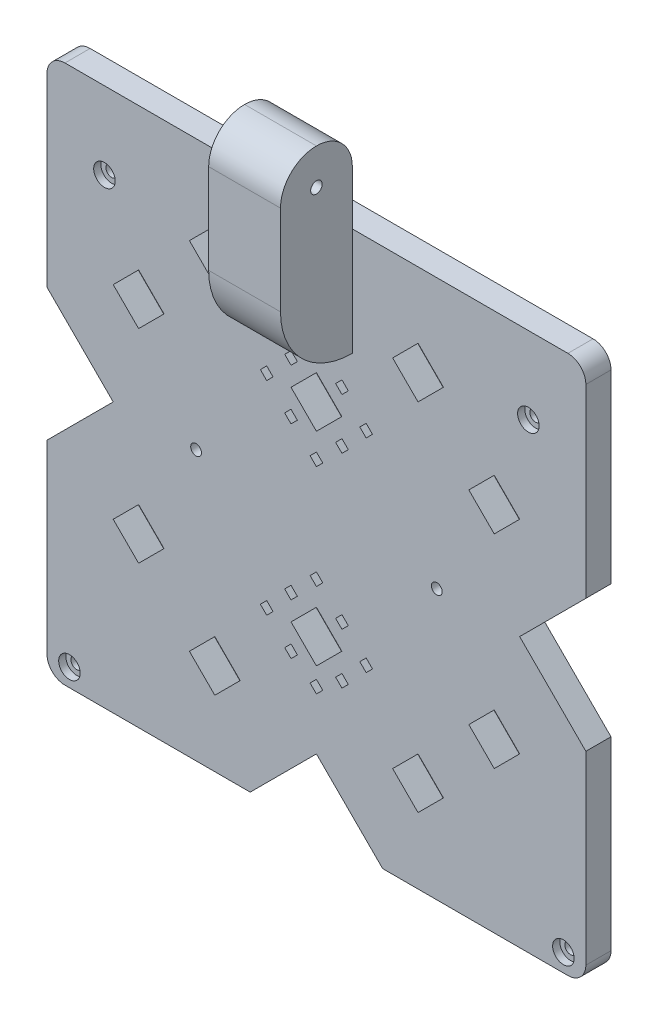
SolidWorks part; units mm, degrees
ref_plane "前基準面" through (0, 0, 0) normal (0, 0, 1) x (1, 0, 0)
ref_plane "上基準面" through (0, 0, 0) normal (0, 1, 0) x (1, 0, 0)
ref_plane "右基準面" through (0, 0, 0) normal (1, 0, 0) x (0, 0, -1)
sketch "草圖1" plane through (0, 0, 0) normal (0, 0, 1) x (1, 0, 0)
  line L1 (-75, 75) -> (75, 75)
  line L2 (-75, 75) -> (-75, -75)
  line L3 (-75, -75) -> (75, -75)
  line L4 (75, 75) -> (75, -75)
  line L5 (-75, 75) -> (75, -75) construction
  line L6 (-75, -75) -> (75, 75) construction
  point P0 (0, 0)
  dimension "D1" = 150
  dimension "D2" = 150
extrude "填料-伸長1" add sketch "草圖1" along normal blind 7 contours L2 L1 L4 L3
sketch "草圖2" plane through (0, 0, 7) normal (0, 0, 1) x (1, 0, 0)
  line L0 (-75, 75) -> (75, -75)
  line L1 (-75, -75) -> (75, 75)
  line L7 (-33.5, 33.5) -> (33.5, -33.5) construction
  line L8 (-33.5, -33.5) -> (33.5, 33.5) construction
  line L21 (-75, 18.8557) -> (18.8557, -75)
  line L22 (-75, 18.4315) -> (18.4315, -75)
  line L23 (-75, 75) -> (-75, -75) construction
  line L24 (-75, -75) -> (75, -75) construction
  line L25 (-18.4315, 75) -> (75, -18.4315)
  line L26 (-75, 75) -> (75, 75) construction
  line L27 (75, 75) -> (75, -75) construction
  line L28 (18.4315, 75) -> (-75, -18.4315)
  line L29 (75, 18.4315) -> (-18.4315, -75)
  line L35 (-75, -18.4315) -> (-56.5685, 0)
  line L36 (-56.5685, 0) -> (-75, 18.4315)
  line L37 (-18.4315, 75) -> (0, 56.5685)
  line L38 (0, 56.5685) -> (18.4315, 75)
  line L39 (-18.4315, 75) -> (18.4315, 75)
  line L40 (75, 18.4315) -> (75, -18.4315)
  line L41 (56.5685, 0) -> (75, 18.4315)
  line L42 (-18.4315, -75) -> (18.4315, -75)
  line L43 (0, -56.5685) -> (-18.4315, -75)
  line L44 (0, -56.5685) -> (18.4315, -75)
  line L45 (-75, 18.8557) -> (-75, 18.4315)
  line L46 (18.8557, -75) -> (18.4315, -75)
  line L47 (-18.8557, -75) -> (-18.4315, -75)
  line L48 (-18.8557, -75) -> (75, 18.8557)
  line L49 (75, 18.8557) -> (75, 18.4315)
  line L50 (-18.8557, 75) -> (-18.4315, 75)
  line L51 (-18.8557, 75) -> (75, -18.8557)
  line L52 (75, -18.8557) -> (75, -18.4315)
  line L53 (18.4315, 75) -> (18.8557, 75)
  line L54 (18.8557, 75) -> (-75, -18.8557)
  line L55 (-75, -18.8557) -> (-75, -18.4315)
  point P8 (0, 0)
  dimension "D8" = 40
  dimension "D2" = 0.3
  dimension "D3" = 0.3
  dimension "D4" = 0.3
  dimension "D5" = 0.3
  dimension "D9" = 40
  dimension "D10" = 40
  dimension "D11" = 40
sketch "草圖3" plane through (0, 0, 7) normal (0, 0, 1) x (1, 0, 0)
  line L0 (-75, 18.4315) -> (-56.5685, 0)
  line L1 (-56.5685, 0) -> (-75, -18.4315)
  line L2 (-75, -18.4315) -> (-75, 18.4315)
  line L3 (18.4315, -75) -> (-18.4315, -75)
  line L4 (-18.4315, -75) -> (0, -56.5685)
  line L5 (0, -56.5685) -> (18.4315, -75)
  line L6 (75, 18.4315) -> (75, -18.4315)
  line L7 (75, -18.4315) -> (56.5685, 0)
  line L8 (56.5685, 0) -> (75, 18.4315)
  line L9 (-18.4315, 75) -> (18.4315, 75)
  line L10 (18.4315, 75) -> (0, 56.5685)
  line L11 (0, 56.5685) -> (-18.4315, 75)
extrude "除料-伸長1" cut sketch "草圖3" against normal blind 7 contours L8 L6 L7 | L5 L3 L4 | L2 L0 L1
sketch "草圖7" plane through (0, 75, 0) normal (0, 1, 0) x (1, 0, 0)
  line L6 (0, 0) -> (0, -7)
  line L7 (-75, 0) -> (75, 0) construction
  line L8 (-75, -7) -> (75, -7) construction
  line L10 (-7.5, 0) -> (7.5, 0)
  line L11 (-7.5, 0) -> (-7.5, -7)
  line L12 (-7.5, -7) -> (7.5, -7)
  line L13 (7.5, 0) -> (7.5, -7)
  line L14 (-7.5, 0) -> (7.5, -7) construction
  line L15 (-7.5, -7) -> (7.5, 0) construction
  point P6 (0, -3.5)
  dimension "D1" = 15
sketch "草圖11" plane through (0, 0, 7) normal (0, 0, 1) x (1, 0, 0)
  line L5 (-28.5, 33.5) -> (-28.5, -33.5)
  line L6 (-28.5, -33.5) -> (28.5, -33.5)
  line L7 (-28.5, -33.5) -> (-28.5, 33.5)
  line L8 (-28.5, 33.5) -> (28.5, 33.5)
  line L9 (28.5, -33.5) -> (28.5, 33.5)
  line L10 (-28.5, -33.5) -> (28.5, 33.5) construction
  line L11 (-28.5, 33.5) -> (28.5, -33.5) construction
  line L13 (-38.5, 0) -> (-38.5, 5)
  line L14 (-38.5, 5) -> (-28.5, 5)
  line L15 (-28.5, 5) -> (-28.5, 0)
  line L16 (-28.5, 0) -> (-28.5, -5)
  line L17 (-28.5, -5) -> (-38.5, -5)
  line L18 (-38.5, -5) -> (-38.5, 0)
  line L19 (-38.5, 5) -> (-28.5, -5)
  line L20 (-28.5, 5) -> (28.5, 5)
  line L21 (28.5, 5) -> (38.5, 5)
  line L22 (38.5, 5) -> (38.5, -5)
  line L23 (38.5, -5) -> (28.5, -5)
  line L24 (28.5, 5) -> (38.5, -5)
  circle A0 centre (-33.5, 0) radius 1.5
  circle A1 centre (33.5, 0) radius 1.5
  point P0 (0, 0)
  point P20 (0, 0)
  dimension "D4" = 10
  dimension "D1" = 67
  dimension "D2" = 67
  dimension "D3" = 10
extrude "除料-伸長3" cut sketch "草圖11" against normal blind 7 contours A0 | A1
sketch "草圖12" plane through (0, 0, 0) normal (0, 0, -1) x (-1, 0, 0)
  line L0 (-75, -65) -> (75, -65)
  line L1 (-75, -18.4315) -> (-75, -75) construction
  line L2 (75, -18.4315) -> (75, -75) construction
  line L3 (-62.5, -75) -> (-62.5, 75)
  line L4 (-18.4315, -75) -> (-75, -75) construction
  line L5 (75, 75) -> (-75, 75) construction
  line L6 (62.5, 75) -> (62.5, -75)
  line L7 (75, 75) -> (-75, 75) construction
  line L8 (75, -75) -> (18.4315, -75) construction
  line L9 (-75, -65) -> (-62.5, -75)
  line L10 (62.5, -65) -> (75, -75)
  line L11 (-65.17, -70) -> (-66.96, -66.8996)
  line L12 (-66.96, -66.8996) -> (-70.54, -66.8996)
  line L13 (-70.54, -66.8996) -> (-72.33, -70)
  line L14 (-72.33, -70) -> (-70.54, -73.1004)
  line L15 (-70.54, -73.1004) -> (-66.96, -73.1004)
  line L16 (-66.96, -73.1004) -> (-65.17, -70)
  line L18 (72.33, -70) -> (70.54, -66.8996)
  line L19 (70.54, -66.8996) -> (66.96, -66.8996)
  line L20 (66.96, -66.8996) -> (65.17, -70)
  line L21 (65.17, -70) -> (66.96, -73.1004)
  line L22 (66.96, -73.1004) -> (70.54, -73.1004)
  line L23 (70.54, -73.1004) -> (72.33, -70)
  circle A0 centre (-68.75, -70) radius 3.1004 construction
  circle A1 centre (68.75, -70) radius 3.1004 construction
  dimension "D1" = 12.5
  dimension "D2" = 12.5
  dimension "D3" = 10
  dimension "D4" = 3.58
  dimension "D5" = 3.58
extrude "除料-伸長4" cut sketch "草圖12" against normal blind 0.5 contours L12 L13 L14 L15 L16 L11 | L18 L19 L20 L21 L22 L23
sketch "草圖13" plane through (0, 0, 0.5) normal (0, 0, -1) x (-1, 0, 0)
  line L0 (-70.54, -66.8996) -> (-66.96, -73.1004)
  line L1 (66.96, -66.8996) -> (70.54, -73.1004)
  line L2 (-65.52, -70) -> (-67.135, -67.2027)
  line L3 (-67.135, -67.2027) -> (-70.365, -67.2027)
  line L4 (-70.365, -67.2027) -> (-71.98, -70)
  line L5 (-71.98, -70) -> (-70.365, -72.7973)
  line L6 (-70.365, -72.7973) -> (-67.135, -72.7973)
  line L7 (-67.135, -72.7973) -> (-65.52, -70)
  line L9 (71.98, -70) -> (70.365, -67.2027)
  line L10 (70.365, -67.2027) -> (67.135, -67.2027)
  line L11 (67.135, -67.2027) -> (65.52, -70)
  line L12 (65.52, -70) -> (67.135, -72.7973)
  line L13 (67.135, -72.7973) -> (70.365, -72.7973)
  line L14 (70.365, -72.7973) -> (71.98, -70)
  circle A0 centre (-68.75, -70) radius 2.7973 construction
  circle A1 centre (68.75, -70) radius 2.7973 construction
  dimension "D1" = 3.23
  dimension "D2" = 3.23
extrude "除料-伸長5" cut sketch "草圖13" against normal blind 2 contours L11 L12 L13 L14 L9 L10 | L3 L4 L5 L6 L7 L2
sketch "草圖14" plane through (0, 0, 2.5) normal (0, 0, -1) x (-1, 0, 0)
  line L0 (65.52, -70) -> (71.98, -70)
  line L1 (-71.98, -70) -> (-65.52, -70)
  circle A0 centre (68.75, -70) radius 1.6
  circle A1 centre (-68.75, -70) radius 1.6
extrude "除料-伸長6" cut sketch "草圖14" against normal blind 3.5 contours A1 | A0
sketch "草圖15" plane through (0, 0, 0) normal (0, 0, -1) x (-1, 0, 0)
  line L0 (-62.5032, 75) -> (-62.5032, -75)
  line L1 (75, 75) -> (-75, 75) construction
  line L2 (-18.4315, -75) -> (-75, -75) construction
  line L3 (62.5, 75) -> (62.5, -75)
  line L4 (75, 75) -> (-75, 75) construction
  line L5 (75, -75) -> (18.4315, -75) construction
  line L6 (-75, -18.4315) -> (-75, -75) construction
  line L7 (75, -18.4315) -> (75, -75) construction
  line L8 (-62.5032, 50) -> (62.5, 50)
  line L10 (75, 75) -> (75, 18.4315) construction
  line L11 (75, 46.7157) -> (75, 75)
  line L12 (-62.5032, 57) -> (62.5, 57)
  line L15 (-55.5032, 57) -> (-55.5032, 50)
  line L16 (55.5, 57) -> (55.5, 50)
  line L17 (55.5, 57) -> (62.5, 50)
  line L18 (-62.5032, 57) -> (-55.5032, 50)
  circle A0 centre (59, 53.5) radius 1.6
  circle A1 centre (-59.0032, 53.5) radius 1.6
  dimension "D1" = 12.4968
  dimension "D2" = 12.5
  dimension "D3" = 125
  dimension "D4" = 7
  dimension "D5" = 7
  dimension "D6" = 7
extrude "除料-伸長7" cut sketch "草圖15" against normal blind 7 contours A1 | A0
sketch "草圖16" plane through (0, 0, 0) normal (0, 0, -1) x (-1, 0, 0)
  line L0 (75, 75) -> (-75, 75) construction
  line L5 (-17.5, 45) -> (17.5, 45)
  line L6 (-17.5, 45) -> (-17.5, 75)
  line L7 (-17.5, 75) -> (17.5, 75)
  line L8 (17.5, 45) -> (17.5, 75)
  line L9 (-17.5, 45) -> (17.5, 75) construction
  line L10 (-17.5, 75) -> (17.5, 45) construction
  line L11 (18.4315, 75) -> (-18.4315, 75) construction
  line L12 (0, 75) -> (0, 60)
  point P0 (-0.3693, 67.6901)
  dimension "D1" = 35
  dimension "D2" = 30
sketch "草圖18" plane through (0, 0, 7) normal (0, 0, 1) x (1, 0, 0)
  line L0 (0, 75) -> (0, 60)
  line L10 (0, 75) -> (-10, 75)
  line L11 (0, 75) -> (10, 75)
  line L12 (-10, 75) -> (-10, 45)
  line L13 (10, 75) -> (10, 45)
  line L14 (10, 45) -> (-10, 45)
  dimension "D1" = 10
  dimension "D2" = 10
extrude "填料-伸長6" add sketch "草圖18" along normal blind 20
fillet "圓角5" radius 20 1 edges at (0, 45, 27)
sketch "草圖20" plane through (0, 75, 0) normal (0, 1, 0) x (1, 0, 0)
  line L1 (-10, -7) -> (10, -7)
  line L2 (-10, -7) -> (-10, -27)
  line L3 (-10, -27) -> (10, -27)
  line L4 (10, -7) -> (10, -27)
extrude "填料-伸長7" add sketch "草圖20" along normal blind 25
fillet "圓角6" radius 10 2 edges at (0, 100, 7) (0, 100, 27)
sketch "草圖21" plane through (-10, 0, 0) normal (-1, 0, 0) x (0, 0, 1)
  circle A0 centre (17, 90) radius 1.6
extrude "除料-伸長8" cut sketch "草圖21" against normal blind 35
sketch "草圖24" plane through (0, 0, 7) normal (0, 0, -1) x (-1, 0, 0)
  line L0 (-10.3123, 85.7865) -> (-30.4726, 85.7865)
  line L1 (-10, 90) -> (-10, 75) construction
  line L2 (-30.4726, 85.7865) -> (-30.4726, 83.7865)
  line L3 (-30.4726, 83.7865) -> (-10, 83.7865)
  line L4 (-10, 83.7865) -> (9.6877, 83.7865)
  line L6 (9.6877, 83.7865) -> (29.5274, 83.7865)
  line L7 (29.5274, 83.7865) -> (29.5274, 85.7865)
  line L8 (29.5274, 85.7865) -> (9.6877, 85.7865)
  line L9 (9.6877, 85.7865) -> (-10.3123, 85.7865)
  dimension "D1" = 2
  dimension "D2" = 60
sketch "草圖25" plane through (0, 0, 7) normal (0, 0, 1) x (1, 0, 0)
  line L0 (0, -75) -> (0, 75) construction
  line L2 (75, 0) -> (-75, 0) construction
  line L5 (-28.2843, -28.2843) -> (-75, -28.2843) construction
  line L6 (-42.4264, -28.2843) -> (-49.4975, -21.2132)
  line L7 (-49.4975, -21.2132) -> (-56.5685, -28.2843)
  line L8 (-56.5685, -28.2843) -> (-49.4975, -35.3553)
  line L9 (-49.4975, -35.3553) -> (-42.4264, -28.2843)
  line L10 (-75, 18.4315) -> (18.4315, -75) construction
  line L11 (-75, -18.4315) -> (-75, -75) construction
  line L12 (-28.2843, -28.2843) -> (-28.2843, -75) construction
  line L13 (-75, -75) -> (-18.4315, -75) construction
  line L14 (-75, -75) -> (75, 75) construction
  line L15 (-21.2132, -49.4975) -> (-28.2843, -42.4264)
  line L16 (-28.2843, -42.4264) -> (-35.3553, -49.4975)
  line L17 (-35.3553, -49.4975) -> (-28.2843, -56.5685)
  line L18 (-28.2843, -56.5685) -> (-21.2132, -49.4975)
  line L19 (75, 18.4315) -> (75, -18.4315) construction
  line L20 (-18.4315, -75) -> (18.4315, -75) construction
  line L21 (-28.2843, 56.5685) -> (-21.2132, 49.4975)
  line L22 (-35.3553, 49.4975) -> (-28.2843, 56.5685)
  line L23 (-28.2843, 42.4264) -> (-35.3553, 49.4975)
  line L24 (-21.2132, 49.4975) -> (-28.2843, 42.4264)
  line L25 (-49.4975, 35.3553) -> (-42.4264, 28.2843)
  line L26 (-56.5685, 28.2843) -> (-49.4975, 35.3553)
  line L27 (-49.4975, 21.2132) -> (-56.5685, 28.2843)
  line L28 (-42.4264, 28.2843) -> (-49.4975, 21.2132)
  line L29 (28.2843, -56.5685) -> (21.2132, -49.4975)
  line L30 (35.3553, -49.4975) -> (28.2843, -56.5685)
  line L31 (28.2843, -42.4264) -> (35.3553, -49.4975)
  line L32 (21.2132, -49.4975) -> (28.2843, -42.4264)
  line L33 (49.4975, -35.3553) -> (42.4264, -28.2843)
  line L34 (56.5685, -28.2843) -> (49.4975, -35.3553)
  line L35 (49.4975, -21.2132) -> (56.5685, -28.2843)
  line L36 (42.4264, -28.2843) -> (49.4975, -21.2132)
  line L37 (56.5685, 28.2843) -> (49.4975, 35.3553)
  line L38 (49.4975, 21.2132) -> (56.5685, 28.2843)
  line L39 (42.4264, 28.2843) -> (49.4975, 21.2132)
  line L40 (49.4975, 35.3553) -> (42.4264, 28.2843)
  line L41 (35.3553, 49.4975) -> (28.2843, 56.5685)
  line L42 (28.2843, 42.4264) -> (35.3553, 49.4975)
  line L43 (21.2132, 49.4975) -> (28.2843, 42.4264)
  line L44 (28.2843, 56.5685) -> (21.2132, 49.4975)
  line L45 (-7.0711, 28.2843) -> (0, 35.3553)
  line L46 (0, -35.3553) -> (7.0711, -28.2843)
  line L47 (7.0711, -28.2843) -> (0, -21.2132)
  line L48 (0, -21.2132) -> (-7.0711, -28.2843)
  line L49 (-7.0711, -28.2843) -> (0, -35.3553)
  line L50 (0, 21.2132) -> (-7.0711, 28.2843)
  line L51 (7.0711, 28.2843) -> (0, 21.2132)
  line L52 (0, 35.3553) -> (7.0711, 28.2843)
  line L97 (0, -21.2132) -> (-7.0588, -21.2132) construction
  line L98 (-7.0772, -22.9871) -> (-5.3095, -21.2194)
  line L99 (-5.3095, -21.2194) -> (-7.0772, -19.4516)
  line L100 (-7.0772, -19.4516) -> (-8.845, -21.2194)
  line L131 (-8.845, -21.2194) -> (-7.0772, -22.9871)
  line L132 (8.8758, -21.2132) -> (7.108, -19.4454)
  line L133 (7.108, -19.4454) -> (5.3402, -21.2132)
  line L134 (5.3402, -21.2132) -> (7.108, -22.981)
  line L135 (7.108, -22.981) -> (8.8758, -21.2132)
  line L136 (8.8758, -35.3917) -> (7.108, -33.6239)
  line L137 (7.108, -33.6239) -> (5.3402, -35.3917)
  line L138 (5.3402, -35.3917) -> (7.108, -37.1594)
  line L139 (7.108, -37.1594) -> (8.8758, -35.3917)
  line L140 (-5.291, -35.3553) -> (-7.0588, -33.5876)
  line L141 (-7.0588, -33.5876) -> (-8.8265, -35.3553)
  line L142 (-8.8265, -35.3553) -> (-7.0588, -37.1231)
  line L143 (-7.0588, -37.1231) -> (-5.291, -35.3553)
  line L144 (-7.0588, -21.2132) -> (-7.0588, -35.3917) construction
  line L145 (-7.0588, -35.3917) -> (7.108, -35.3917) construction
  line L146 (7.108, -35.3917) -> (7.108, -21.2132) construction
  line L147 (7.108, -21.2132) -> (0, -21.2132) construction
  line L148 (-7.0588, 37.1231) -> (-5.291, 35.3553)
  line L149 (-8.8265, 35.3553) -> (-7.0588, 37.1231)
  line L150 (-7.0588, 33.5876) -> (-8.8265, 35.3553)
  line L151 (-5.291, 35.3553) -> (-7.0588, 33.5876)
  line L152 (7.108, 37.1594) -> (8.8758, 35.3917)
  line L153 (5.3402, 35.3917) -> (7.108, 37.1594)
  line L154 (7.108, 33.6239) -> (5.3402, 35.3917)
  line L155 (8.8758, 35.3917) -> (7.108, 33.6239)
  line L156 (7.108, 22.981) -> (8.8758, 21.2132)
  line L157 (5.3402, 21.2132) -> (7.108, 22.981)
  line L158 (7.108, 19.4454) -> (5.3402, 21.2132)
  line L159 (8.8758, 21.2132) -> (7.108, 19.4454)
  line L160 (-8.845, 21.2194) -> (-7.0772, 22.9871)
  line L161 (-7.0772, 19.4516) -> (-8.845, 21.2194)
  line L162 (-5.3095, 21.2194) -> (-7.0772, 19.4516)
  line L163 (-7.0772, 22.9871) -> (-5.3095, 21.2194)
  line L164 (0, 42.1231) -> (1.7678, 40.3553)
  line L165 (-12.0711, -28.2843) -> (-13.8388, -26.5165)
  line L166 (-13.8388, -26.5165) -> (-15.6066, -28.2843)
  line L167 (-15.6066, -28.2843) -> (-13.8388, -30.052)
  line L168 (-13.8388, -30.052) -> (-12.0711, -28.2843)
  line L169 (15.6066, -28.2843) -> (13.8388, -26.5165)
  line L170 (13.8388, -26.5165) -> (12.0711, -28.2843)
  line L171 (12.0711, -28.2843) -> (13.8388, -30.052)
  line L172 (13.8388, -30.052) -> (15.6066, -28.2843)
  line L173 (1.7678, -14.4454) -> (0, -12.6777)
  line L174 (0, -12.6777) -> (-1.7678, -14.4454)
  line L175 (-1.7678, -14.4454) -> (0, -16.2132)
  line L176 (0, -16.2132) -> (1.7678, -14.4454)
  line L177 (1.7678, -40.3553) -> (0, -38.5876)
  line L178 (0, -38.5876) -> (-1.7678, -40.3553)
  line L179 (-1.7678, -40.3553) -> (0, -42.1231)
  line L180 (0, -42.1231) -> (1.7678, -40.3553)
  line L181 (-1.7678, 40.3553) -> (0, 42.1231)
  line L182 (0, 38.5876) -> (-1.7678, 40.3553)
  line L183 (1.7678, 40.3553) -> (0, 38.5876)
  line L184 (13.8388, 30.052) -> (15.6066, 28.2843)
  line L185 (12.0711, 28.2843) -> (13.8388, 30.052)
  line L186 (13.8388, 26.5165) -> (12.0711, 28.2843)
  line L187 (15.6066, 28.2843) -> (13.8388, 26.5165)
  line L188 (-13.8388, 30.052) -> (-12.0711, 28.2843)
  line L189 (-15.6066, 28.2843) -> (-13.8388, 30.052)
  line L190 (-13.8388, 26.5165) -> (-15.6066, 28.2843)
  line L191 (-12.0711, 28.2843) -> (-13.8388, 26.5165)
  line L192 (0, 16.2132) -> (1.7678, 14.4454)
  line L193 (-1.7678, 14.4454) -> (0, 16.2132)
  line L194 (0, 12.6777) -> (-1.7678, 14.4454)
  line L195 (1.7678, 14.4454) -> (0, 12.6777)
  circle A0 centre (-49.4975, -28.2843) radius 5 construction
  circle A1 centre (-28.2843, -49.4975) radius 5 construction
  circle A2 centre (0, -28.2843) radius 5 construction
  circle A24 centre (-7.0772, -21.2194) radius 1.25 construction
  circle A25 centre (7.108, -21.2132) radius 1.25 construction
  circle A26 centre (7.108, -35.3917) radius 1.25 construction
  circle A27 centre (-7.0588, -35.3553) radius 1.25 construction
  circle A28 centre (-13.8388, -28.2843) radius 1.25 construction
  circle A29 centre (13.8388, -28.2843) radius 1.25 construction
  circle A30 centre (0, -14.4454) radius 1.25 construction
  circle A31 centre (0, -40.3553) radius 1.25 construction
  dimension "D1" = 10
  dimension "D2" = 10
  dimension "D3" = 10
  dimension "D4" = 10
  dimension "D5" = 10
  dimension "D6" = 2.5
  dimension "D7" = 2.5
  dimension "D8" = 2.5
  dimension "D9" = 2.5
  dimension "D10" = 5
  dimension "D11" = 2.5
  dimension "D12" = 2.5
  dimension "D13" = 2.5
  dimension "D14" = 2.5
  dimension "D15" = 5
  dimension "D16" = 5
  dimension "D17" = 5
  dimension "D18" = 5
extrude "除料-伸長9" cut sketch "草圖25" against normal blind 7
sketch "草圖26" plane through (0, 0, 7) normal (0, 0, 1) x (1, 0, 0)
  line L0 (0, 75) -> (0, -75) construction
  line L1 (-18.4315, -75) -> (18.4315, -75) construction
  circle A1 centre (-59, 53.5) radius 3
  circle A2 centre (-68.75, -70) radius 3
  circle A3 centre (68.75, -70) radius 3
  circle A5 centre (59, 53.5) radius 3
extrude "除料-伸長10" cut sketch "草圖26" against normal blind 2
fillet "圓角7" radius 5 4 edges at (-75, 75, 3.5) (75, 75, 3.5) (75, -75, 3.5) (-75, -75, 3.5)
sketch "草圖27" plane through (0, 0, 0) normal (0, 0, -1) x (-1, 0, 0)
  line L0 (-35.2321, -3) -> (-31.7679, -3)
  line L1 (-30.0359, 0) -> (-31.7679, 3)
  line L2 (-31.7679, 3) -> (-35.2321, 3)
  line L3 (-35.2321, 3) -> (-36.9641, 0)
  line L4 (-36.9641, 0) -> (-35.2321, -3)
  line L5 (-31.7679, -3) -> (-30.0359, 0)
  line L6 (0, 75) -> (0, -56.5685) construction
  line L7 (18.4315, 75) -> (-18.4315, 75) construction
  line L8 (31.7679, -3) -> (30.0359, 0)
  line L9 (35.2321, -3) -> (31.7679, -3)
  line L10 (36.9641, 0) -> (35.2321, -3)
  line L11 (35.2321, 3) -> (36.9641, 0)
  line L12 (31.7679, 3) -> (35.2321, 3)
  line L13 (30.0359, 0) -> (31.7679, 3)
  circle A0 centre (-33.5, 0) radius 3 construction
  dimension "D1" = 3
extrude "除料-伸長11" cut sketch "草圖27" against normal blind 2
